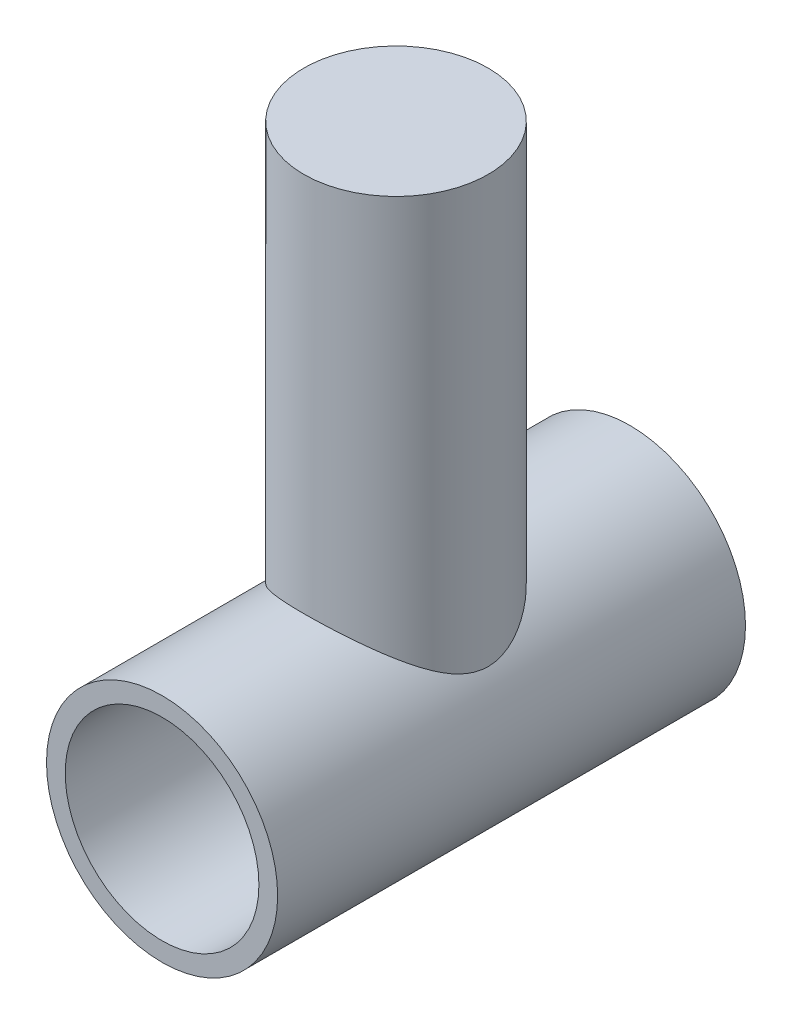
SolidWorks part; units mm, degrees
ref_plane "Front Plane" through (0, 0, 0) normal (0, 0, 1) x (1, 0, 0)
ref_plane "Top Plane" through (0, 0, 0) normal (0, 1, 0) x (1, 0, 0)
ref_plane "Right Plane" through (0, 0, 0) normal (1, 0, 0) x (0, 0, -1)
sketch "Sketch1" plane through (0, 0, 0) normal (0, 0, 1) x (1, 0, 0)
  circle A0 centre (0, 0) radius 10.35
  circle A1 centre (0, 0) radius 12.35
  dimension "D1" = 20.7
  dimension "D2" = 24.7
extrude "Boss-Extrude1" add sketch "Sketch1" along normal blind 50
ref_plane "Plane1" through (0, 11, 0) normal (0, 1, 0) x (1, 0, 0)
sketch "Sketch2" plane through (0, 11, 0) normal (0, 1, 0) x (1, 0, 0)
  line L0 (0, 0) -> (0, -50) construction
  line L1 (-12.35, -50) -> (12.35, -50) construction
  circle A0 centre (0, -25) radius 9.85
  dimension "D1" = 19.7
extrude "Boss-Extrude2" add sketch "Sketch2" along normal blind 42 separate body
extrude "Boss-Extrude3" add sketch "Sketch2<3>" against normal blind 6
sketch "Sketch2<3>" plane through (0, 11, 0) normal (0, 1, 0) x (1, 0, 0) same geometry as "Sketch2"
extrude "Cut-Extrude1" cut sketch "Sketch1<2>" along normal blind 51 contours A0 region at (0, 0, 0)
sketch "Sketch1<2>" plane through (0, 0, 0) normal (0, 0, 1) x (1, 0, 0) same geometry as "Sketch1"
